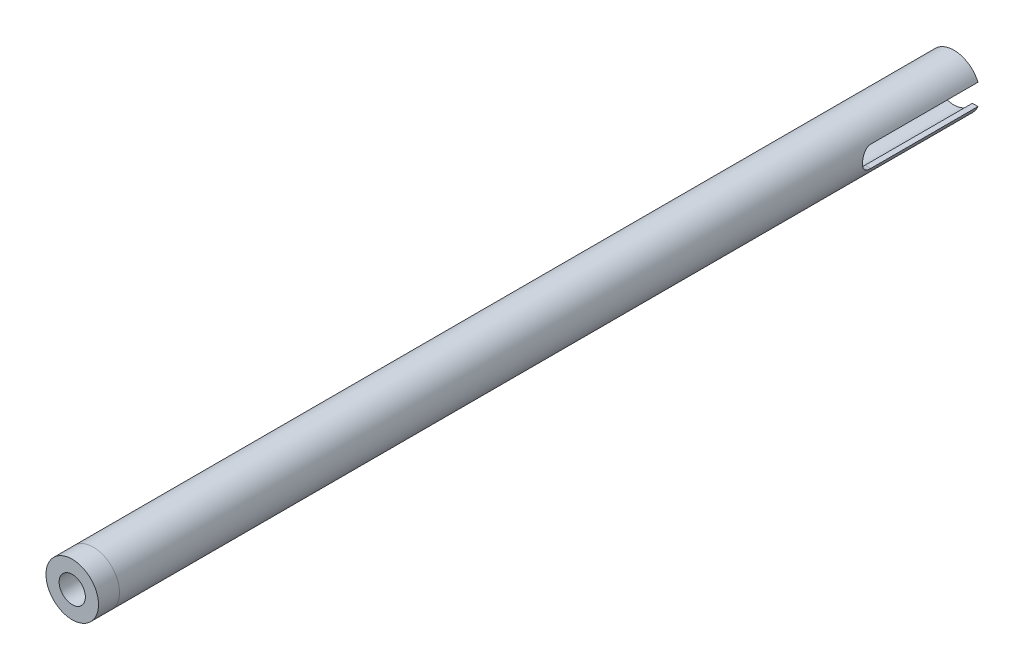
SolidWorks part; units mm, degrees
material "AISI 4130 Steel, annealed at 865C"
ref_plane "Front Plane" through (0, 0, 0) normal (0, 0, 1) x (1, 0, 0)
ref_plane "Top Plane" through (0, 0, 0) normal (0, 1, 0) x (1, 0, 0)
ref_plane "Right Plane" through (0, 0, 0) normal (1, 0, 0) x (0, 0, -1)
sketch "Axis" plane through (0, 0, 0) normal (0, 1, 0) x (1, 0, 0)
  line L0 (0, 0) -> (0, 266.3731) construction
  line L1 (0, 0) -> (0, -28.575) construction
  line L2 (0, 266.3731) -> (-7.9375, 266.3731) construction
  line L3 (0, 289.8013) -> (-10.3187, 259.3446) construction
  dimension "D1" = 28.575
  dimension "D2" = 7.9375
sketch "Sketch1" plane through (0, 0, 0) normal (0, 0, 1) x (1, 0, 0)
  line L0 (-7.9375, 0) -> (7.9375, 0) construction
  line L1 (-7.2748, 3.175) -> (7.2748, 3.175)
  line L2 (-7.2748, -3.175) -> (7.2748, -3.175)
  circle A0 centre (0, 0) radius 7.9375
  circle A1 centre (0, 0) radius 6.4135
  circle A2 centre (0, 0) radius 3.9688
  dimension "D1" = 15.875
  dimension "D3" = 7.9375
  dimension "D2" = 1.524
  dimension "D4" = 6.35
extrude "Threaded insert 1-1" add sketch "Sketch1" against normal blind 6.35 contours A2 L1 A1 | A1 L1 A0 | A2 L0 A1 L1 | A1 L0 A0 L1 | L0 A1 L2 A0 | L0 A2 L2 A1 | A2 L2 A1 | A1 L2 A0 | L0 A1 L2 A2 | L0 A0 L2 A1 | A0 L0 A1 L1 | A1 L0 A2 L1 region at (4.7887, 1.6543, 0) region at (4.7887, -1.6543, 0) region at (6.9234, 1.6163, 0) region at (6.9234, -1.6163, 0) region at (-4.7887, -1.6543, 0) region at (-4.7887, 1.6543, 0) region at (0, 4.6159, 0) region at (0, -4.6159, 0) region at (0, 6.5666, 0) region at (6.4237, -3.3281, 0) region at (-6.9234, -1.6163, 0) region at (-6.9234, 1.6163, 0)
extrude "Threaded insert 1-2" add sketch "Sketch1<3>" against normal blind 9.525 from surface contours A2 L1 A1 | A2 L0 A1 L1 | L0 A2 L2 A1 | A2 L2 A1 | L0 A1 L2 A2 | A1 L0 A2 L1 region at (4.7887, 1.6543, 0) region at (4.7887, -1.6543, 0) region at (-4.7887, -1.6543, 0) region at (-4.7887, 1.6543, 0) region at (0, 4.6159, 0) region at (0, -4.6159, 0) starting at face at (7.9375, 0, -6.35)
sketch "Sketch1<3>" plane through (0, 0, 0) normal (0, 0, 1) x (1, 0, 0) same geometry as "Sketch1"
extrude "A-arm tube" add sketch "Sketch1<4>" against normal up to vertex (266.3731 mm away) from surface separate body contours A1 L1 A0 | A1 L0 A0 L1 | L0 A1 L2 A0 | A1 L2 A0 | L0 A0 L2 A1 | A0 L0 A1 L1 region at (6.9234, 1.6163, 0) region at (6.9234, -1.6163, 0) region at (0, 6.5666, 0) region at (6.4237, -3.3281, 0) region at (-6.9234, -1.6163, 0) region at (-6.9234, 1.6163, 0) up to point (0, 0, -266.3731) starting at face at (6.4135, 0, -6.35)
sketch "Sketch1<4>" plane through (0, 0, 0) normal (0, 0, 1) x (1, 0, 0) same geometry as "Sketch1"
extrude "Apex slot" cut sketch "Sketch1<5>" along normal blind 35.56 from surface contours A0 L0 A1 L1 | L0 A0 L2 A1 | A1 L0 A0 L1 | L0 A1 L2 A0 region at (6.9234, 1.6163, 0) region at (6.9234, -1.6163, 0) region at (-6.9234, -1.6163, 0) region at (-6.9234, 1.6163, 0) starting at face at (6.4135, 0, -266.3731)
sketch "Sketch1<5>" plane through (0, 0, 0) normal (0, 0, 1) x (1, 0, 0) same geometry as "Sketch1"
fillet "Fillet1" radius 3.175 4 edges at (-6.4237, 3.175, -230.8131) (-6.4237, -3.175, -230.8131) (6.4237, -3.175, -230.8131) (6.4237, 3.175, -230.8131)
equation "\"tube diameter\"= 5 / 8"
equation "\"tube thickness\"= .06"
equation "\"apex thickness\"= .25"
equation "\"tube slot\"= 1.4"
equation "\"D1@Sketch1\"=\"tube diameter\""
equation "\"D2@Sketch1\"=\"tube thickness\""
equation "\"threaded insert hole\"= .3125"
equation "\"D3@Sketch1\"=\"threaded insert hole\""
equation "\"D4@Sketch1\"=\"apex thickness\""
equation "\"D1@Apex slot\" = \"tube slot\""
equation "\"D1@Fillet1\"=\"apex thickness\"/2"
